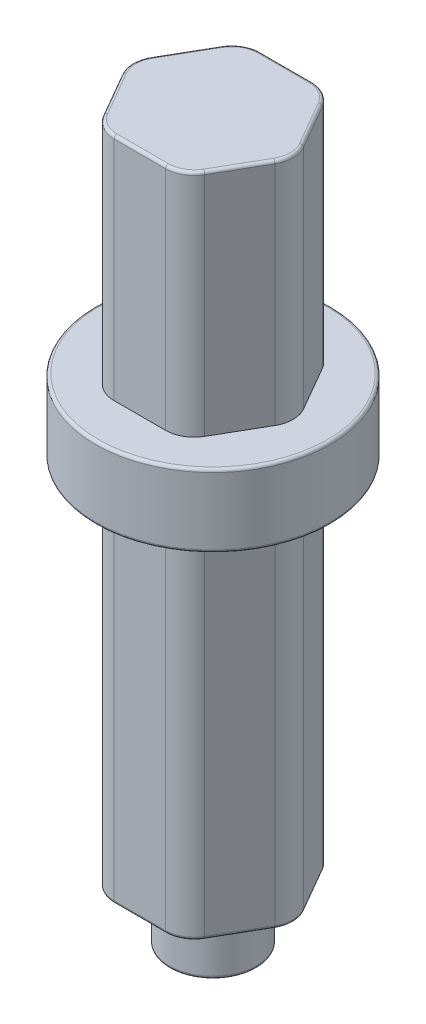
SolidWorks part; units mm, degrees
ref_plane "Front Plane" through (0, 0, 0) normal (0, 0, 1) x (1, 0, 0)
ref_plane "Top Plane" through (0, 0, 0) normal (0, 1, 0) x (1, 0, 0)
ref_plane "Right Plane" through (0, 0, 0) normal (1, 0, 0) x (0, 0, -1)
sketch "Sketch1" plane through (0, 0, 0) normal (0, 1, 0) x (1, 0, 0)
  circle A0 centre (0, 0) radius 3.8
  dimension "D1" = 7.6
extrude "MotorMountShell" add sketch "Sketch1" along normal blind 5.08
sketch "Sketch2" plane through (0, 0, 0) normal (0, -1, 0) x (1, 0, 0)
  line L0 (-1.45, 1.9125) -> (-1.45, -1.9125)
  line L1 (1.45, 1.9125) -> (1.45, -1.9125)
  circle A0 centre (0, 0) radius 2.4
  dimension "D1" = 4.8
  dimension "D2" = 2.9
extrude "MotorMount" cut sketch "Sketch2" against normal blind 5.08 contours L1 A0 L0 region at (0, 0, 0)
sketch "Sketch3" plane through (0, 5.08, 0) normal (0, 1, 0) x (1, 0, 0)
  line L1 (3.6806, -6.375) -> (7.3612, 0)
  line L2 (7.3612, 0) -> (3.6806, 6.375)
  line L3 (3.6806, 6.375) -> (-3.6806, 6.375)
  line L4 (-3.6806, 6.375) -> (-7.3612, 0)
  line L5 (-7.3612, 0) -> (-3.6806, -6.375)
  line L6 (-3.6806, -6.375) -> (3.6806, -6.375)
  circle A1 centre (0, 0) radius 6.375 construction
  dimension "D1" = 12.75
extrude "Shaft" add sketch "Sketch3" along normal blind 58
sketch "Sketch4" plane through (0, 0, 0) normal (0, 0, 1) x (1, 0, 0)
  line L0 (0, 0) -> (0, 19.302) construction
  line L1 (-3.6806, 63.08) -> (3.6806, 63.08) construction
  line L2 (0, 36.73) -> (10.25, 36.73)
  line L3 (0, 36.73) -> (0, 43.08)
  line L4 (0, 43.08) -> (10.25, 43.08)
  line L5 (10.25, 36.73) -> (10.25, 43.08)
  dimension "D1" = 10.25
  dimension "D3" = 6.35
  dimension "D2" = 20
revolve "Collar" add sketch "Sketch4" angle 360 about L0
sketch "Sketch5" plane through (0, 0, 0) normal (0, -1, 0) x (1, 0, 0)
  circle A0 centre (-1.45, 1.9125) radius 0.005
  circle A1 centre (1.45, 1.9125) radius 0.005
  circle A2 centre (-1.45, -1.9125) radius 0.005
  circle A3 centre (1.45, -1.9125) radius 0.005
  dimension "D1" = 0.01
extrude "MountRound" cut sketch "Sketch5" against normal up to surface (5.08 mm away) up to face at (0, 5.08, 0)
fillet "Fillet1" radius 0.254 16 edges at (0, 5.08, 3.8) (5.5209, 5.08, 3.1875) (5.5209, 5.08, -3.1875) (0, 5.08, -6.375) (-5.5209, 5.08, -3.1875) (-5.5209, 5.08, 3.1875) (0, 5.08, 6.375) (-5.5209, 63.08, 3.1875) (-5.5209, 63.08, -3.1875) (0, 63.08, -6.375) (5.5209, 63.08, -3.1875) (5.5209, 63.08, 3.1875) (0, 63.08, 6.375) (0, 0, 3.8) (0, 43.08, -10.25) (0, 36.73, -10.25)
fillet "Fillet2" radius 2.5 24 edges at (-3.6377, 5.1544, 6.3006) (3.6377, 5.1544, 6.3006) (-7.2753, 5.1544, 0) (-7.2753, 63.0056, 0) (-3.6377, 63.0056, 6.3006) (-3.6377, 5.1544, -6.3006) (3.6377, 63.0056, -6.3006) (3.6377, 5.1544, -6.3006) (7.2753, 5.1544, 0) (7.2753, 63.0056, 0) (3.6377, 63.0056, 6.3006) (3.6806, 52.953, 6.375) (7.3612, 52.953, 0) (7.3612, 21.032, 0) (3.6806, 21.032, -6.375) (3.6806, 52.953, -6.375) (-3.6806, 21.032, -6.375) (-3.6806, 52.953, 6.375) (-7.3612, 52.953, 0) (-7.3612, 21.032, 0) (3.6806, 21.032, 6.375) (-3.6806, 21.032, 6.375) (-3.6377, 63.0056, -6.3006) (-3.6806, 52.953, -6.375)
equation "\"D1@Sketch3\"= \"HEXSHAFT_D\""
equation "\"CB_W\" = 5"
equation "\"CW_DEPTH\" = 1"
equation "\"PIN_SPACING\" = 2.54"
equation "\"PIN_D\" = 1"
equation "\"PCB_THICK\" = 1.5"
equation "\"TAP_HOLE\" = 2.5"
equation "\"SCREW_HOLE\" = 3"
equation "\"SLIPRING_D\" = 12.4"
equation "\"SLIPRING_MOUNTOD\" = 15"
equation "\"SLIPRING_MOUNTTHICK\" = 8"
equation "\"SLIPRING_MOUNT_LEGH\" = 12"
equation "\"PITCH_D\"= 44.45"
equation "\"HEX_D\"= 12.7"
equation "\"BODY_Y\"= 70"
equation "\"BODY_X\"= 60"
equation "\"BODY_Z\"= 120"
equation "\"BODY_THICK\"= 3"
equation "\"BODY_TOPTHICK\"= 4"
equation "\"STAND_R\" = 3"
equation "\"STAND_ZOFF\" = 10"
equation "\"STAND_XOFF\" = 5"
equation "\"MOTOR_ZOFF\" = 25"
equation "\"MOTOR_MOUNTANGLE\" = 120"
equation "\"MOTOR_D\"= 28"
equation "\"MOTOR_H\"= 19"
equation "\"MOTOR_HOLEDIST\"= 35"
equation "\"MOTOR_SHAFTOFF\" = 8"
equation "\"DRVR_Y\" = 31"
equation "\"DRVR_Z\" = 27"
equation "\"DRVR_YOFF\" = 15"
equation "\"DRVR_ARDOFF\" = 10"
equation "\"BEARING_OD\" = 28.575"
equation "\"BEARING_ID\" = 12.7"
equation "\"BEARING_THICK\" = 7.925"
equation "\"BEARING_FLANGE_D\" = 31.242"
equation "\"BEARING_FLANGETHICK\" = 1.575"
equation "\"BMOUNT_X\" = 30"
equation "\"BMOUNT_HEXID\" = 15"
equation "\"BMOUNT_HEXTHICK\" = 2"
equation "\"BMOUNT_HEXH\" = 35"
equation "\"BMOUNT_HOLEX\" = 4*\"PIN_SPACING\""
equation "\"BMOUNT_HOLEZ\" = 4*\"PIN_SPACING\""
equation "\"BMOUNT_SCREWH\" = 5"
equation "\"MBOARD_MHOLEX\" = 10*\"PIN_SPACING\""
equation "\"MBOARD_MHOLEXOFF\" = 2*\"PIN_SPACING\""
equation "\"MBOARD_MHOLEZ\" = 9*\"PIN_SPACING\""
equation "\"MBOARD_POGOSPACING\" = 1*\"PIN_SPACING\""
equation "\"MBOARD_POGOX\" = 7*\"PIN_SPACING\""
equation "\"MBOARD_POGOXOFF\" = 1*\"PIN_SPACING\""
equation "\"MBOARD_POGOZ\" = 7*\"PIN_SPACING\""
equation "\"MBOARD_W\" = 28*\"PIN_SPACING\""
equation "\"SHAFT_BASEID\" = 12.7"
equation "\"SHAFT_BASEOD\" = \"SHAFT_BASEID\" + 2*3"
equation "\"SHAFT_BASEHOLEH\" = 10"
equation "\"SHAFT_MOUNTOD\" = \"BMOUNT_HEXID\""
equation "\"SHAFT_MOUNTH\" = \"BMOUNT_HEXH\" "
equation "\"SHAFT_D\" = 18"
equation "\"HEXSHAFT_D\" = 12.75"
equation "\"HEXSHAFT_FILLET\" = 2.5"
equation "\"COLLAR_OD\" = 20.5"
equation "\"D1@Sketch4\"=\"COLLAR_OD\"/2"
equation "\"SHAFT_MOUNTTHICK\" = 1.5"
equation "\"DRIVESHAFT_COLLARH\" = 20"
equation "\"COLLAR_THICK\" = 6.35"
equation "\"D3@Sketch4\"=\"COLLAR_THICK\""
equation "\"D2@Sketch4\"=\"DRIVESHAFT_COLLARH\""
equation "\"DRIVESHAFT_LENGTH\" = 58"
equation "\"D1@Shaft\"=\"DRIVESHAFT_LENGTH\""
equation "\"DRIVESHAFT_HOLED\" = 4.8"
equation "\"DRIVESHAFT_HOLEW\" = 2.9"
equation "\"D1@Sketch2\"=\"DRIVESHAFT_HOLED\""
equation "\"D2@Sketch2\"=\"DRIVESHAFT_HOLEW\""
equation "\"DRIVESHAFT_MOUNTD\" = 7.6"
equation "\"D1@Sketch1\"=\"DRIVESHAFT_MOUNTD\""
equation "\"D1@Fillet2\"=\"HEXSHAFT_FILLET\""
equation "\"DRIVENSHAFT_THICK\" = 1.5"
equation "\"DRIVENSHAFT_TOPLENGTH\" = 35"
equation "\"DRIVENSHAFT_BOTTOMLENGTH\" = 25.4"
equation "\"DRIVENSHAFT_HOLEH\" = \"SHAFT_BASEHOLEH\" + 12.7"
